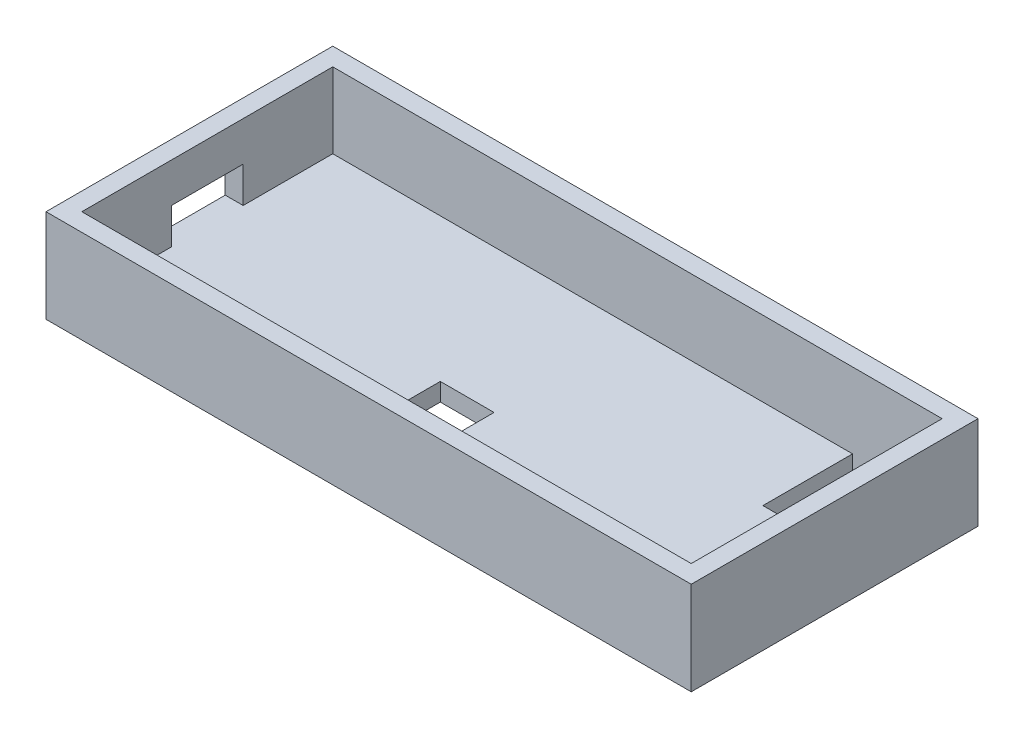
SolidWorks part; units mm, degrees
ref_plane "Front Plane" through (0, 0, 0) normal (0, 0, 1) x (1, 0, 0)
ref_plane "Top Plane" through (0, 0, 0) normal (0, 1, 0) x (1, 0, 0)
ref_plane "Right Plane" through (0, 0, 0) normal (1, 0, 0) x (0, 0, -1)
sketch "Sketch2" plane through (0, 0, 0) normal (0, 1, 0) x (1, 0, 0)
  line L0 (-15, -35) -> (-15, -15)
  line L1 (-90, 40) -> (90, 40)
  line L2 (-90, 40) -> (-90, -40)
  line L3 (-90, -40) -> (90, -40)
  line L4 (90, 40) -> (90, -40)
  line L5 (-90, 40) -> (90, -40) construction
  line L6 (-90, -40) -> (90, 40) construction
  line L7 (-85, 35) -> (85, 35)
  line L8 (-85, 35) -> (-85, -35)
  line L9 (-85, -35) -> (85, -35)
  line L10 (85, 35) -> (85, -35)
  line L11 (-85, 35) -> (85, -35) construction
  line L12 (-85, -35) -> (85, 35) construction
  line L13 (85, -35) -> (60, -35)
  line L14 (85, -35) -> (85, -10)
  line L21 (85, 35) -> (60, 35)
  line L22 (85, 35) -> (85, 10)
  line L27 (85, 10) -> (60, 10)
  line L28 (60, 35) -> (60, 10)
  line L29 (-15, -15) -> (-85, -15)
  line L31 (-15, -15) -> (0, -15)
  line L32 (-15, -15) -> (-15, -5)
  line L33 (-15, -5) -> (0, -5)
  line L34 (0, -15) -> (0, -5)
  circle A0 centre (1889.3403, 685.8778) radius 127
  circle A2 centre (75.9261, -27.8287) radius 5
  point P0 (0, 0)
  point P6 (0, 0)
  point P15 (-381, 381)
  point P21 (-15, 15)
  dimension "D7" = 20
  dimension "D1" = 180
  dimension "D2" = 80
  dimension "D3" = 170
  dimension "D4" = 70
  dimension "D5" = 25
  dimension "D6" = 25
  dimension "D8" = 70
  dimension "D11" = 15
  dimension "D12" = 10
extrude "Boss-Extrude1" add sketch "Sketch2" along normal blind 26 contours L4 L1 L2 L3 L7 L10 L9 L8 region at (0, 0, -38.0302)
extrude "Boss-Extrude2" add sketch "Sketch2<4>" along normal blind 5 contours L0 L29 L8 L9 | L34 L31 L0 L9 L10 L27 L28 L7 L8 L29 L32 L33 A2 region at (-50, 0, 25) region at (2.0577, 0, -2.5526)
sketch "Sketch2<4>" plane through (0, 0, 0) normal (0, 1, 0) x (1, 0, 0) same geometry as "Sketch2"
sketch "Sketch3" plane through (-90, 0, 0) normal (-1, 0, 0) x (0, 0, 1)
  line L0 (0, 0) -> (0, 10)
  line L1 (0, 10) -> (0, 26)
  line L2 (-10, 15) -> (10, 15)
  line L3 (-10, 15) -> (-10, 5)
  line L4 (-10, 5) -> (10, 5)
  line L5 (10, 15) -> (10, 5)
  line L6 (-10, 15) -> (10, 5) construction
  line L7 (-10, 5) -> (10, 15) construction
  line L8 (-40, 26) -> (40, 26) construction
  dimension "D1" = 10
  dimension "D2" = 20
  dimension "D3" = 10
extrude "Cut-Extrude1" cut sketch "Sketch3" against normal blind 5 contours L3 L4 L0 L1 L2 | L5 L2 L1 L0 L4 | L3 L2 L5 L4 region at (-90, 10, -5) region at (-90, 10, 5)
